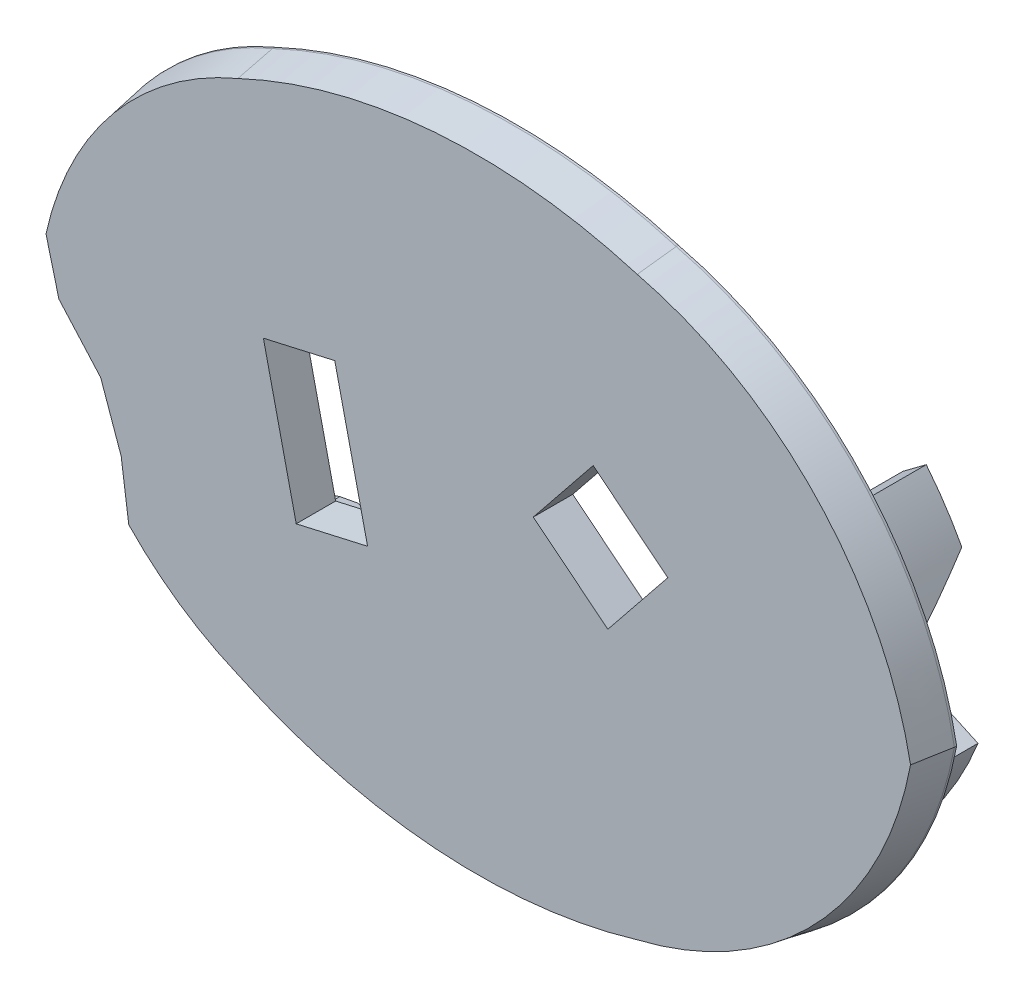
SolidWorks part; units mm, degrees
ref_plane "Front Plane" through (0, 0, 0) normal (0, 0, 1) x (1, 0, 0)
ref_plane "Top Plane" through (0, 0, 0) normal (0, 1, 0) x (1, 0, 0)
ref_plane "Right Plane" through (0, 0, 0) normal (1, 0, 0) x (0, 0, -1)
sketch "Sketch1" plane through (0, 0, 0) normal (0, 0, 1) x (1, 0, 0)
  line L4 (-58.8092, -17.6893) -> (-56.9717, -24.8216)
  line L5 (-56.9717, -24.8216) -> (-51.3295, -31.1692)
  line L6 (-51.3295, -31.1692) -> (-48.6583, -38.7135)
  line L7 (-48.6583, -38.7135) -> (-47.6189, -46.3583)
  arc A6 (59.1764, -21.378) -> (21.7862, 18.1981) centre (9.9454, -30.4393) ccw
  arc A7 (21.7862, 18.1981) -> (-32.4781, 14.1122) centre (0, -54.8435) ccw
  arc A8 (-32.4781, 14.1122) -> (-58.8092, -17.6893) centre (-15.11, -27.0699) ccw
  arc A9 (-32.4781, -56.8682) -> (-47.6189, -46.3583) centre (-15.11, -15.6861) cw
  arc A10 (21.7862, -60.9541) -> (-32.4781, -56.8682) centre (0, 12.0875) cw
  arc A11 (59.1764, -21.378) -> (21.7862, -60.9541) centre (9.9454, -12.3167) cw
  point P0 (0, 0)
  dimension "D2" = 76.2214
  dimension "D3" = 50.058
  dimension "D4" = 44.6947
  dimension "D5" = 76.2214
  dimension "D1" = 12.0875
extrude "Boss-Extrude1" add sketch "Sketch1" along normal blind 5.3
chamfer "Chamfer1" distance 5 angle 10 10 edges at (46.3323, -46.6939, 5.3) (-5.723, -63.9188, 5.3) (-40.5962, -52.4022, 5.3) (-48.1386, -42.5359, 5.3) (-49.9939, -34.9414, 5.3) (-54.1506, -27.9954, 5.3) (-57.8905, -21.2554, 5.3) (-49.5358, 1.4341, 5.3) (46.3323, 3.9379, 5.3) (-5.723, 21.1628, 5.3) first distance on face at (43.4068, -43.93, 2.65) first distance on face at (-5.5345, -61.415, 2.65) first distance on face at (-40.3223, -52.0077, 2.65) first distance on face at (-48.1386, -42.5359, 2.65) first distance on face at (-49.9939, -34.9414, 2.65) first distance on face at (-54.1506, -27.9954, 2.65) first distance on face at (-57.8905, -21.2554, 2.65) first distance on face at (-47.5897, -0.1772, 2.65) first distance on face at (43.4068, 1.174, 2.65) first distance on face at (-5.5345, 18.659, 2.65)
sketch "Sketch2" plane through (0, 0, 0) normal (0, 0, -1) x (-1, 0, 0)
  line L7 (31.2763, 9.847) -> (27.7371, 3.911)
  line L8 (42.8096, -9.0722) -> (46.8763, -3.3933)
  line L10 (26.6903, -46.7388) -> (31.033, -53.1744)
  line L11 (39.0108, -42.3852) -> (40.3977, -36.6901)
  line L14 (40.3977, -36.6901) -> (43.5033, -30.0469)
  line L15 (43.5033, -30.0469) -> (48.6913, -24.7392)
  line L16 (48.6913, -24.7392) -> (53.3702, -18.2488)
  line L20 (-19.9716, 14.4087) -> (-19.195, 12.4343)
  line L27 (-41.465, -3.5137) -> (-44.5942, -1.1798)
  line L28 (-44.8646, -27.0758) -> (-51.5468, -30.1376)
  line L29 (-32.8861, -43.1983) -> (-38.7588, -48.0169)
  line L30 (-44.8646, -9.307) -> (-41.465, -3.5137)
  line L31 (39.0108, -42.3852) -> (33.018, -43.1064)
  line L32 (33.018, -43.1064) -> (26.6903, -46.7388)
  line L33 (43.1871, -44.3376) -> (39.0108, -42.3852)
  line L34 (-49.8231, -14.3904) -> (-51.9148, -14.0339)
  line L35 (-41.465, -3.5137) -> (-44.8646, -9.307)
  line L36 (9.7339, 13.9491) -> (10.6003, 16.4649)
  line L37 (-4.7237, 14.7755) -> (-4.8826, 17.1405)
  line L38 (-32.8861, -43.1983) -> (-31.6707, -49.9851)
  line L39 (-44.8646, -9.307) -> (-49.8231, -14.3904)
  line L40 (44.1329, -37.3808) -> (43.1871, -44.3376)
  line L41 (46.5637, -30.5155) -> (44.1329, -37.3808)
  line L42 (51.6981, -24.7392) -> (46.5637, -30.5155)
  line L43 (53.3702, -18.2488) -> (51.6981, -24.7392)
  line L44 (-31.6707, -49.9851) -> (-24.6864, -53.5082)
  line L45 (-24.6864, -53.5082) -> (-25.5321, -55.8827)
  arc A3 (27.7371, 3.911) -> (42.8096, -9.0722) centre (19.0626, -21.4001) cw
  arc A8 (-4.7237, 14.7755) -> (9.7339, 13.9491) centre (-0.0333, -30.0469) cw
  arc A9 (-44.8646, -27.0758) -> (-32.8861, -43.1983) centre (-10.3568, -13.9486) ccw
  arc A10 (-19.195, 12.4343) -> (-43.0296, -2.3468) centre (-9.4062, -29.9574) ccw
  arc A11 (-51.5468, -30.1376) -> (-25.5321, -55.8827) centre (-9.1964, -13.3597) ccw
  arc A12 (31.033, -53.1744) -> (43.1871, -44.3376) centre (13.6039, -16.4259) ccw
  arc A13 (46.8763, -3.3933) -> (31.2763, 9.847) centre (13.6039, -26.7852) ccw
  arc A14 (10.6003, 16.4649) -> (-4.8826, 17.1405) centre (-0.1461, -52.0591) ccw
  arc A15 (-19.9716, 14.4087) -> (-51.9148, -14.0339) centre (-9.1964, -29.8513) ccw
  dimension "D1" = 4.7237
  dimension "D2" = 14.7755
extrude "Boss-Extrude2" add sketch "Sketch2" along normal blind 10.5 contours L27 A15 L34 L39 L30 | L28 A11 L29 A9 | L10 A12 L33 L31 L32 | L8 A13 L7 A3 region at (-37.7924, 1.217, 0) region at (-34.4304, -46.9883, 0) region at (46.6249, -7.7509, 0) region at (42.7824, -37.6935, 0)
ref_plane "Plane1" through (0, 0, -2.5) normal (0, 0, -1) x (-1, 0, 0)
sketch "Sketch3" plane through (0, 0, -2.5) normal (0, 0, -1) x (-1, 0, 0)
  line L0 (-32.8823, -43.1938) -> (-38.7551, -48.0124)
  line L1 (-19.9679, 14.4133) -> (-19.1913, 12.4389)
  line L2 (-49.8194, -14.3859) -> (-51.9111, -14.0293)
  line L3 (-44.8609, -9.3025) -> (-49.8194, -14.3859)
  line L4 (-44.8609, -9.3025) -> (-41.4613, -3.5092)
  line L5 (-41.4613, -3.5092) -> (-44.8609, -9.3025)
  line L6 (-41.4613, -3.5092) -> (-44.5905, -1.1753)
  line L7 (43.1908, -44.3331) -> (39.0145, -42.3807)
  line L10 (31.28, 9.8515) -> (27.7408, 3.9155)
  line L11 (42.8133, -9.0676) -> (46.88, -3.3888)
  line L12 (39.0145, -42.3807) -> (40.4014, -36.6856)
  line L13 (40.4014, -36.6856) -> (43.507, -30.0424)
  line L14 (43.507, -30.0424) -> (48.695, -24.7347)
  line L15 (48.695, -24.7347) -> (53.374, -18.2443)
  line L16 (53.374, -18.2443) -> (51.7019, -24.7347)
  line L17 (51.7019, -24.7347) -> (46.5674, -30.511)
  line L18 (46.5674, -30.511) -> (44.1366, -37.3763)
  line L19 (44.1366, -37.3763) -> (43.1908, -44.3331)
  line L20 (26.694, -46.7343) -> (31.0367, -53.1699)
  line L27 (33.0217, -43.1019) -> (26.694, -46.7343)
  line L28 (39.0145, -42.3807) -> (33.0217, -43.1019)
  line L29 (9.7376, 13.9536) -> (10.604, 16.4694)
  line L30 (-4.72, 14.78) -> (-4.8789, 17.145)
  line L31 (-32.8823, -43.1938) -> (-31.667, -49.9806)
  line L32 (-31.667, -49.9806) -> (-24.6826, -53.5036)
  line L33 (-24.6826, -53.5036) -> (-25.5284, -55.8781)
  line L34 (-44.8609, -27.0713) -> (-51.5431, -30.1331)
  arc A0 (-19.1913, 12.4389) -> (-43.0259, -2.3423) centre (-9.4024, -29.9528) ccw
  arc A1 (-19.9679, 14.4133) -> (-51.9111, -14.0293) centre (-9.1927, -29.8468) ccw
  arc A4 (42.8133, -9.0676) -> (27.7408, 3.9155) centre (19.0663, -21.3956) ccw
  arc A9 (46.88, -3.3888) -> (31.28, 9.8515) centre (13.6077, -26.7806) ccw
  arc A10 (31.0367, -53.1699) -> (43.1908, -44.3331) centre (13.6077, -16.4213) ccw
  arc A11 (10.604, 16.4694) -> (-4.8789, 17.145) centre (-0.1424, -52.0546) ccw
  arc A12 (9.7376, 13.9536) -> (-4.72, 14.78) centre (-0.0295, -30.0424) ccw
  arc A13 (-51.5431, -30.1331) -> (-25.5284, -55.8781) centre (-9.1927, -13.3552) ccw
  arc A14 (-44.8609, -27.0713) -> (-32.8823, -43.1938) centre (-10.3531, -13.9441) ccw
  dimension "D1" = 14.78
  dimension "D2" = 4.72
extrude "Boss-Extrude3" add sketch "Sketch3" against normal up to surface (2.5 mm away) contours A12 L29 A11 L30 | L19 L18 L17 L16 L15 L14 L13 L12 L7 | L0 A13 L33 L32 L31 | L1 A1 L6 A0 region at (32.2068, -49.9475, -2.5) region at (32.3788, 7.2635, -2.5) region at (-44.8258, -33.1689, -2.5) region at (-2.8429, 15.9279, -2.5) up to face at (-34.6702, -46.0617, 0)
chamfer "Chamfer2" distance 6 angle 55 1 edges at (50.869, -14.2121, -10.5) first distance on face at (46.6374, -8.4252, -10.5)
chamfer "Chamfer3" distance 6 angle 53 1 edges at (35.8224, -45.6076, -10.5) first distance on face at (42.5671, -37.5104, -10.5)
chamfer "Chamfer4" distance 5 angle 60 1 edges at (-29.5067, 6.879, -10.5) first distance on face at (-29.5067, 6.879, -5.25)
sketch "Sketch4" plane through (0, 0, -10.5) normal (0, 0, -1) x (-1, 0, 0)
  line L5 (43.1871, -44.3376) -> (39.4463, -40.5968)
  line L6 (39.0108, -42.3852) -> (39.4463, -40.5968)
  line L7 (39.0108, -42.3852) -> (43.1871, -44.3376)
  point P3 (39.0108, -42.3852)
  dimension "D1" = 1.8407
  dimension "D2" = 5.2903
extrude "Boss-Extrude4" add sketch "Sketch4" against normal blind 10.5
chamfer "Chamfer5" distance 6.5 angle 50 1 edges at (-41.3167, -42.4672, -10.5) first distance on face at (-41.3143, -42.4648, -3.25)
sketch "Sketch5" plane through (0, 0, 0) normal (0, 0, -1) x (-1, 0, 0)
  line L0 (-25.6533, -15.9145) -> (-15.6301, -7.8656)
  line L1 (-25.6533, -15.9145) -> (-17.6043, -25.9377)
  line L2 (-15.6301, -7.8656) -> (-7.5811, -17.8888)
  line L3 (-17.6043, -25.9377) -> (-7.5811, -17.8888)
  line L4 (19.0955, -13.0208) -> (28.6875, -15.2008)
  line L5 (19.0955, -13.0208) -> (14.6864, -32.421)
  line L6 (28.6875, -15.2008) -> (24.2783, -34.601)
  line L7 (14.6864, -32.421) -> (24.2783, -34.601)
  dimension "D1" = 12.855
  dimension "D2" = 19.895
  dimension "D3" = 9.8366
  dimension "D4" = 15.6301
  dimension "D5" = 7.8656
  dimension "D6" = 13.0208
  dimension "D7" = 19.0955
extrude "Cut-Extrude1" cut sketch "Sketch5" against normal blind 10.5
